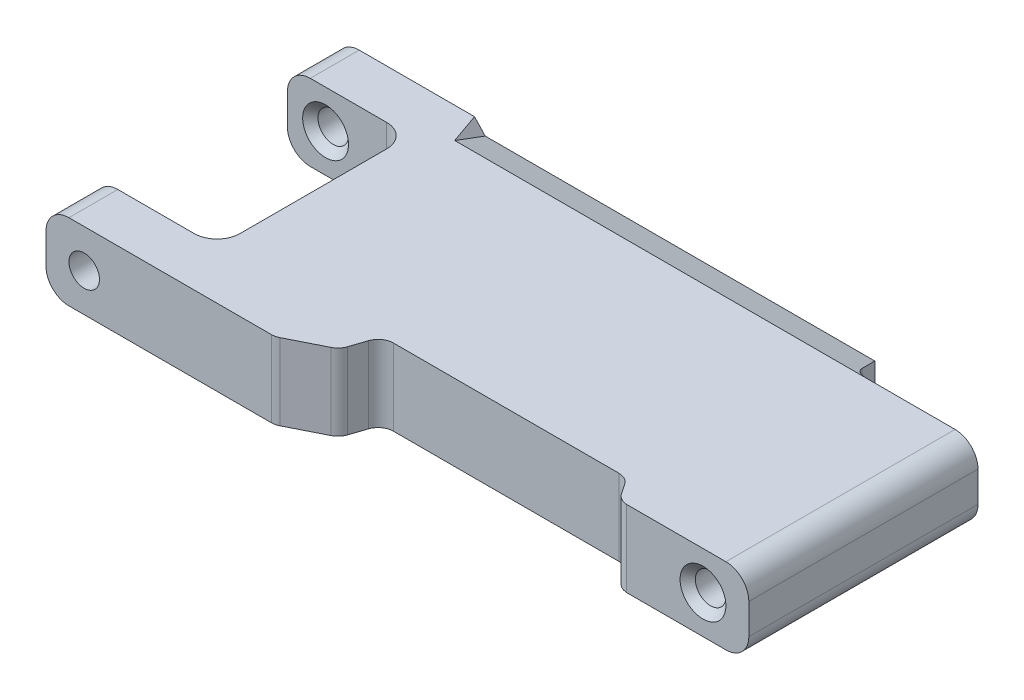
SolidWorks part; units mm, degrees
ref_plane "Front Plane" through (0, 0, 0) normal (0, 0, 1) x (1, 0, 0)
ref_plane "Top Plane" through (0, 0, 0) normal (0, 1, 0) x (1, 0, 0)
ref_plane "Right Plane" through (0, 0, 0) normal (1, 0, 0) x (0, 0, -1)
ref_plane "Plane1" through (0, 0, 0) normal (0, 1, 0) x (1, 0, 0)
sketch "Sketch1" plane through (0, 0, 0) normal (0, 1, 0) x (1, 0, 0)
  line L0 (-35.25, 0) -> (-35.25, -6.4)
  line L1 (-35.25, -6.4) -> (-22.25, -6.4)
  line L2 (-19.25, -9.4) -> (-19.25, -28.6)
  line L3 (-22.25, -31.6) -> (-35.25, -31.6)
  line L4 (-35.25, -31.6) -> (-35.25, -38)
  line L5 (-35.25, -38) -> (-5.75, -38)
  line L6 (-4.8528, -37.7875) -> (-0.3841, -35.5446)
  line L7 (0.6161, -34.3896) -> (1.3007, -32.3358)
  line L8 (3.198, -30.9683) -> (32.698, -30.9683)
  line L9 (34.3636, -31.8611) -> (35.194, -33.1102)
  line L10 (36.75, -34) -> (52.75, -34)
  line L11 (52.75, -34) -> (52.75, -4)
  line L12 (52.75, -4) -> (38.136, -4)
  line L13 (36.2633, -2.7022) -> (35.25, 0)
  line L14 (35.25, 0) -> (-35.25, 0)
  arc A0 (-22.25, -6.4) -> (-19.25, -9.4) centre (-22.25, -9.4) cw
  arc A1 (-19.25, -28.6) -> (-22.25, -31.6) centre (-22.25, -28.6) cw
  arc A2 (-5.75, -38) -> (-4.8528, -37.7875) centre (-5.75, -36) ccw
  arc A3 (-0.3841, -35.5446) -> (0.6161, -34.3896) centre (-1.2813, -33.7571) ccw
  arc A4 (1.3007, -32.3358) -> (3.198, -30.9683) centre (3.198, -32.9683) cw
  arc A5 (32.698, -30.9683) -> (34.3636, -31.8611) centre (32.698, -32.9683) cw
  arc A6 (35.194, -33.1102) -> (36.75, -34) centre (36.8596, -32.003) ccw
  arc A7 (38.136, -4) -> (36.2633, -2.7022) centre (38.136, -2) cw
  point P2 (0, 0)
  dimension "D3" = 2
  dimension "D9" = 3
  dimension "D11" = 2
  dimension "D13" = 2
  dimension "D15" = 2
  dimension "D17" = 1.5
  dimension "D1" = 30
  dimension "D2" = 14.614
  dimension "D4" = 2.886
  dimension "D5" = 70.5
  dimension "D6" = 6.4
  dimension "D7" = 13
  dimension "D8" = 19.2
  dimension "D10" = 29.5
  dimension "D12" = 5
  dimension "D14" = 2.1648
  dimension "D16" = 29.5
  dimension "D18" = 16
  dimension "D19" = 69.444
  dimension "D20" = 153.348
  dimension "D21" = 135.087
extrude "Boss-Extrude1" add sketch "Sketch1" along normal blind 10
fillet "Fillet1" radius 3 6 edges at (-35.25, 10, 3.2) (-35.25, 10, 34.8) (-35.25, 0, 34.8) (-35.25, 0, 3.2) (52.75, 0, 19) (52.75, 10, 19)
ref_plane "Plane2" through (38.136, 0, 0) normal (1, 0, 0) x (0, 0, -1)
sketch "Sketch2" plane through (38.136, 0, 0) normal (1, 0, 0) x (0, 0, -1)
  line L0 (-4, 10) -> (0, 10)
  line L1 (0, 10) -> (0, 8.5)
  line L2 (0, 10) -> (0, 0) construction
  line L3 (0, 8.5) -> (-4, 10)
  dimension "D1" = 1.5
extrude "Cut-Extrude1" cut sketch "Sketch2" against normal blind 55.386
chamfer "Chamfer1" distance 1.5 angle 45 1 edges at (-17.25, 9.25, 2)
ref_plane "Plane4" through (0, 5, 0) normal (0, 1, 0) x (1, 0, 0)
mirror "Mirror3" about plane through (0, 5, 0) normal (0, 1, 0) of "Cut-Extrude1", "Chamfer1"
hole_wizard "CSK for M4 SFHCS1" positions "Sketch3" profile "Sketch4" countersink size "M4" standard "ANSI Metric" end condition through all
sketch "Sketch3" plane through (0, 0, 6.4) normal (0, 0, 1) x (1, 0, 0)
  line L0 (-30.25, 10) -> (-30.25, 5) construction
  line L1 (-32.25, 10) -> (-22.25, 10) construction
  line L2 (-30.25, 5) -> (-30.25, 0) construction
  line L3 (-32.25, 0) -> (-22.25, 0) construction
  line L5 (-30.25, 5) -> (-35.25, 5) construction
  line L6 (-35.25, 7) -> (-35.25, 3) construction
  point P0 (-30.25, 5)
  point P57 (0, 0)
  dimension "D1" = 5
sketch "Sketch4" plane through (-30.25, 5, 6.4) normal (1, 0, 0) x (0, -1, 0)
  line L0 (0, 0) -> (0, 6.4)
  line L1 (0, 6.4) -> (2, 6.4)
  line L2 (2, 6.4) -> (2, 1)
  line L3 (2, 1) -> (3, 0)
  line L5 (3, 0) -> (0, 0)
  line L6 (-2, 1) -> (-3, 0) construction
  line L11 (0, -6.35) -> (0, 107.95) construction
  dimension "Thru Hole Dia." = 4
  dimension "Thru Hole Depth" = 6.4
  dimension "Near C'Sink Dia." = 6
  dimension "Near C'Sink Angle" = 90
ref_plane "Plane3" through (0, 0, 19) normal (0, 0, 1) x (1, 0, 0)
mirror "Mirror1" about plane through (0, 0, 19) normal (0, 0, 1) of "CSK for M4 SFHCS1"
hole_wizard "CSK for M4 SFHCS2" positions "Sketch5" profile "Sketch6" countersink size "M4" standard "ANSI Metric" end condition through all
sketch "Sketch5" plane through (0, 0, 34) normal (0, 0, 1) x (1, 0, 0)
  line L0 (46.75, 5) -> (46.75, 10) construction
  line L1 (36.75, 10) -> (49.75, 10) construction
  line L3 (46.75, 5) -> (46.75, 0) construction
  line L4 (36.75, 0) -> (49.75, 0) construction
  line L6 (46.75, 5) -> (52.75, 5) construction
  line L7 (52.75, 7) -> (52.75, 3) construction
  point P0 (46.75, 5)
  dimension "D1" = 6
sketch "Sketch6" plane through (46.75, 5, 34) normal (1, 0, 0) x (0, -1, 0)
  line L0 (0, 0) -> (0, 34)
  line L1 (0, 34) -> (2, 34)
  line L2 (2, 34) -> (2, 1)
  line L3 (2, 1) -> (3, 0)
  line L5 (3, 0) -> (0, 0)
  line L6 (-2, 1) -> (-3, 0) construction
  line L11 (0, -6.35) -> (0, 107.95) construction
  dimension "Thru Hole Dia." = 4
  dimension "Thru Hole Depth" = 34
  dimension "Near C'Sink Dia." = 6
  dimension "Near C'Sink Angle" = 90
mirror "Mirror2" about plane through (0, 0, 19) normal (0, 0, 1) of "CSK for M4 SFHCS2"
sketch "Sketch7" plane through (0, 0, 0) normal (0, 0, -1) x (-1, 0, 0)
  line L0 (-31.25, 5) -> (-35.25, 5) construction
  line L1 (-35.25, 8.5) -> (-35.25, 1.5) construction
  circle A0 centre (-31.25, 5) radius 1.5
  circle A1 centre (-23.75, 5) radius 1.5
  circle A2 centre (-16.25, 5) radius 1.5
  circle A3 centre (-8.75, 5) radius 1.5
  circle A4 centre (-1.25, 5) radius 1.5
  circle A5 centre (6.25, 5) radius 1.5
  circle A6 centre (13.75, 5) radius 1.5
  point P2 (0, 0)
  dimension "D1" = 3
  dimension "D2" = 4
  dimension "D4" = 7.5
  dimension "D3" = 7
extrude "Cut-Extrude2" cut sketch "Sketch7" against normal blind 24
